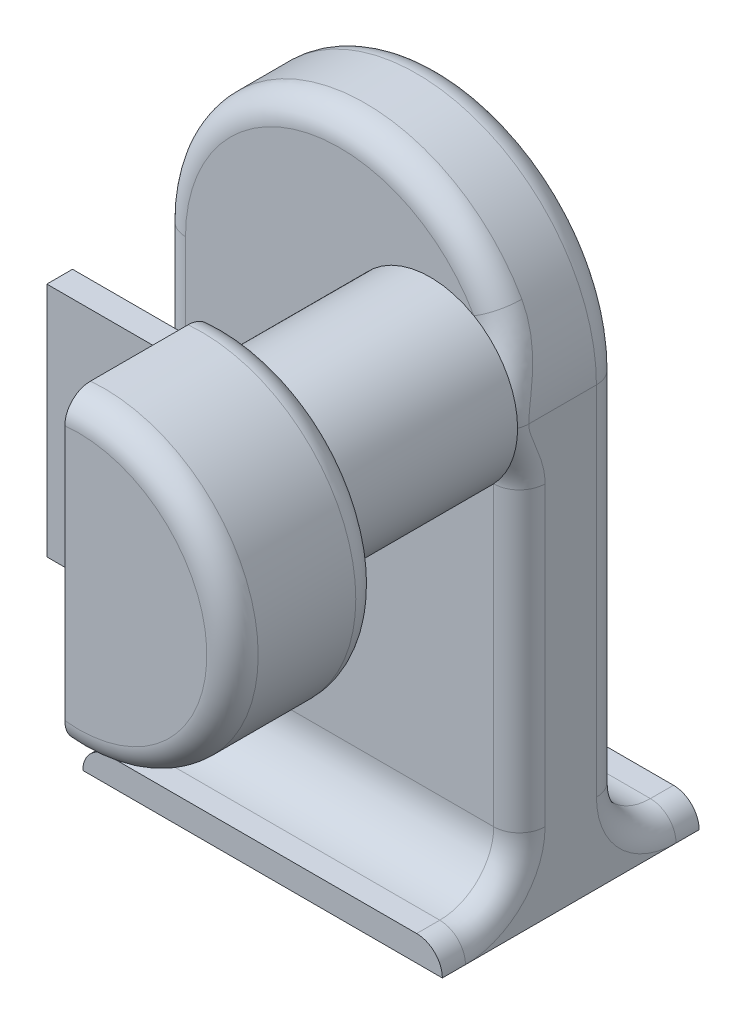
SolidWorks part; units mm, degrees
ref_plane "Front Plane" through (0, 0, 0) normal (0, 0, 1) x (1, 0, 0)
ref_plane "Top Plane" through (0, 0, 0) normal (0, 1, 0) x (1, 0, 0)
ref_plane "Right Plane" through (0, 0, 0) normal (1, 0, 0) x (0, 0, -1)
sketch "Sketch1" plane through (0, 0, 0) normal (0, 0, 1) x (1, 0, 0)
  line L0 (-7, 0) -> (-7, -16)
  line L1 (-7, -16) -> (7, -16)
  line L2 (7, -16) -> (7, 0)
  arc A0 (-7, 0) -> (7, 0) centre (0, 0) cw
  dimension "D1" = 7
  dimension "D2" = 16
extrude "Boss-Extrude1" add sketch "Sketch1" along normal mid plane 4
sketch "Sketch2" plane through (0, 0, 2) normal (0, 0, 1) x (1, 0, 0)
  circle A0 centre (3.53, 0) radius 3.4
  point P3 (0, 0)
  dimension "D1" = 6.8
  dimension "D2" = 3.53
extrude "Boss-Extrude2" add sketch "Sketch2" along normal blind 7.9
sketch "Sketch3" plane through (0, 0, 9.9) normal (0, 0, 1) x (1, 0, 0)
  line L0 (3.53, 4.6) -> (-2.5, 4.6)
  line L1 (2.5, 4.6) -> (-2.5, 4.6) construction
  line L2 (2.5, 4.6) -> (2.5, -4.6) construction
  line L3 (2.5, -4.6) -> (-2.5, -4.6) construction
  line L4 (-2.5, 4.6) -> (-2.5, -4.6)
  line L5 (2.5, 4.6) -> (-2.5, -4.6) construction
  line L6 (2.5, -4.6) -> (-2.5, 4.6) construction
  line L7 (3.53, -4.6) -> (-2.5, -4.6)
  circle A0 centre (3.53, 0) radius 3.4 construction
  circle A1 centre (3.53, 0) radius 3.4 construction
  arc A2 (3.53, 4.6) -> (3.53, -4.6) centre (3.53, 0) cw
  point P0 (0, 0)
  dimension "D1" = 5
  dimension "D2" = 9.2
extrude "Boss-Extrude3" add sketch "Sketch3" along normal blind 1
sketch "Sketch4" plane through (0, -16, 0) normal (0, -1, 0) x (1, 0, 0)
  line L5 (-7, 5) -> (7, 5)
  line L6 (-7, 5) -> (-7, -5)
  line L7 (-7, -5) -> (7, -5)
  line L8 (7, 5) -> (7, -5)
  line L9 (-7, 5) -> (7, -5) construction
  line L10 (-7, -5) -> (7, 5) construction
  line L14 (-7, -2) -> (7, -2)
  line L15 (7, -2) -> (7, 2)
  line L16 (7, 2) -> (-7, 2)
  line L17 (-7, 2) -> (-7, -2)
  line L18 (-7, -2) -> (7, -2) construction
  line L19 (7, -2) -> (7, 2) construction
  line L20 (7, 2) -> (-7, 2) construction
  line L21 (-7, 2) -> (-7, -2) construction
  point P0 (0, 0)
  dimension "D1" = 0
  dimension "D2" = 10
extrude "Boss-Extrude4" add sketch "Sketch4" along normal blind 1
fillet "Fillet2" radius 2.1 2 edges
fillet "Fillet1" radius 1 14 edges at (0, 7, 2) (0, 7, -2) (7, -15.3849, -2.6151) (-7, -15.3849, -2.6151) (7, -15.3849, 2.6151) (-7, -15.3849, 2.6151)
ref_plane "Plane1" through (0, 0, 9.9) normal (0, 0, 1) x (1, 0, 0)
sketch "Sketch5" plane through (0, 0, 9.9) normal (0, 0, 1) x (1, 0, 0)
  line L0 (3, 5.9765) -> (3, -5.9765)
  arc A0 (3.53, -4.6) -> (3.53, 4.6) centre (3.53, 0) ccw construction
  arc A1 (3.53, -4.6) -> (3.53, 4.6) centre (3.53, 0) ccw construction
  arc A2 (3, -5.9765) -> (3, 5.9765) centre (3.53, 0) ccw
  dimension "D1" = 12
  dimension "D2" = 0.53
extrude "Boss-Extrude5" add sketch "Sketch5" along normal blind 5.8
fillet "Fillet4" radius 1 2 edges at (9.53, 0, 9.9) (9.53, 0, 15.7)
fillet "Fillet5" radius 1 1 edges at (6.93, 0, 9.9)
